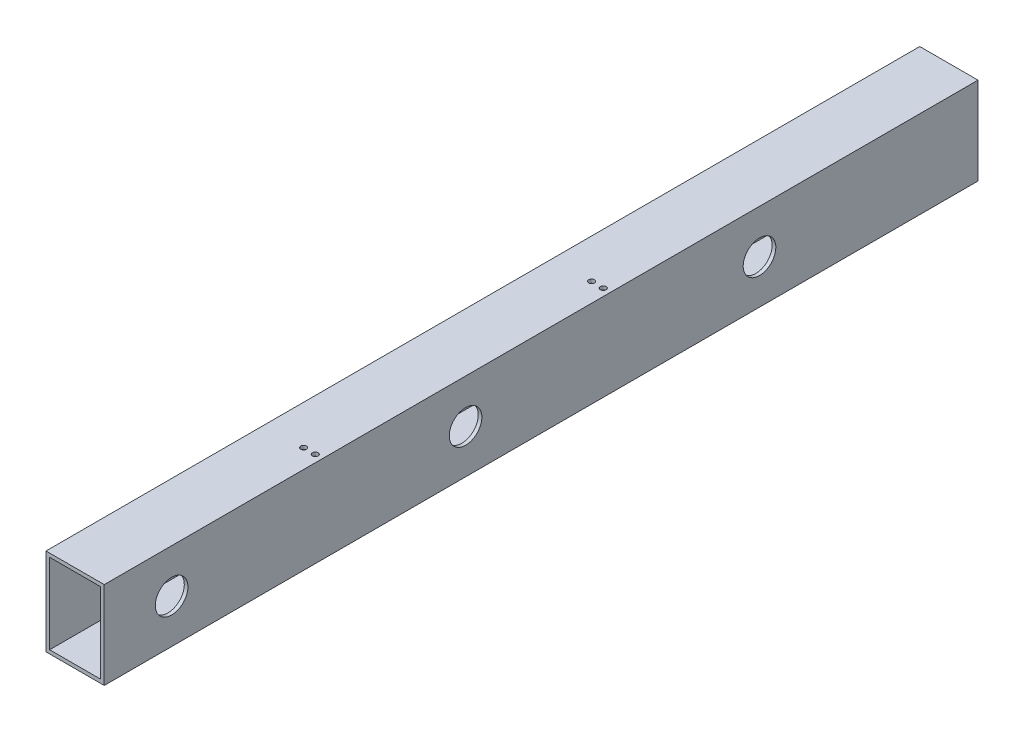
SolidWorks part; units mm, degrees
ref_plane "Front Plane" through (0, 0, 0) normal (0, 0, 1) x (1, 0, 0)
ref_plane "Top Plane" through (0, 0, 0) normal (0, 1, 0) x (1, 0, 0)
ref_plane "Right Plane" through (0, 0, 0) normal (1, 0, 0) x (0, 0, -1)
sketch "Sketch1" plane through (0, 0, 0) normal (0, 0, 1) x (1, 0, 0)
  line L0 (0, 38.1) -> (0, 34.925) construction
  line L1 (-25.4, 38.1) -> (25.4, 38.1)
  line L2 (-25.4, 38.1) -> (-25.4, -38.1)
  line L3 (-25.4, -38.1) -> (25.4, -38.1)
  line L4 (25.4, 38.1) -> (25.4, -38.1)
  line L5 (-25.4, 38.1) -> (25.4, -38.1) construction
  line L6 (-25.4, -38.1) -> (25.4, 38.1) construction
  line L7 (-22.225, 34.925) -> (22.225, 34.925)
  line L8 (-22.225, 34.925) -> (-22.225, -34.925)
  line L9 (-22.225, -34.925) -> (22.225, -34.925)
  line L10 (22.225, 34.925) -> (22.225, -34.925)
  line L11 (22.225, 0) -> (25.4, 0) construction
  line L12 (-22.225, 0) -> (-25.4, 0) construction
  line L13 (0, -34.925) -> (0, -38.1) construction
  point P0 (0, 0)
  dimension "D1" = 76.2
  dimension "D2" = 50.8
  dimension "D3" = 3.175
extrude "Boss-Extrude1" add sketch "Sketch1" along normal blind 762
sketch "Sketch2" plane through (0, 38.1, 0) normal (0, 1, 0) x (1, 0, 0)
  line L0 (-26.9875, -190.549) -> (26.9875, -190.549) construction
  line L1 (-25.4, 0) -> (25.4, 0)
  line L2 (-25.4, 0) -> (-25.4, -762)
  line L3 (-25.4, -762) -> (25.4, -762)
  line L4 (25.4, 0) -> (25.4, -762)
  line L5 (-26.4963, -703.2466) -> (26.4963, -703.2466) construction
  line L6 (0, -703.2466) -> (0, -190.549) construction
  line L7 (0, 0) -> (0, -190.549) construction
  line L8 (-74.6125, -402.6047) -> (-73.6301, -528.6965) construction
  line L9 (-74.1213, -465.6506) -> (-23.8125, -465.6506) construction
  line L10 (-23.8125, -465.6506) -> (26.9875, -465.6506) construction
  line L11 (21.8023, -571.6147) -> (25.4, -571.6147) construction
  line L12 (21.8023, -569.9256) -> (21.8023, -573.3038) construction
  line L13 (21.8023, -571.6147) -> (0, -571.6147) construction
  line L14 (0, -322.121) -> (25.4, -322.121) construction
  dimension "D1" = 190.549
  dimension "D2" = 512.6976
  dimension "D3" = 126.0917
  dimension "D4" = 50.3088
  dimension "D5" = 50.8
  dimension "D6" = 53.975
  dimension "D7" = 52.9926
  dimension "D8" = 275.1016
  dimension "D9" = 131.6319
  dimension "D10" = 131.572
ref_plane "Plane1" through (25.4, 0, 0) normal (1, 0, 0) x (0, 0, -1)
sketch "Sketch4" plane through (25.4, 0, 0) normal (1, 0, 0) x (0, 0, -1)
  line L0 (-703.2466, 38.1) -> (-703.2466, 0) construction
  line L1 (-703.2466, 38.1) -> (-190.549, 38.1) construction
  line L2 (-190.549, 38.1) -> (-190.549, 0) construction
  line L3 (0, 38.1) -> (-190.549, 38.1) construction
  line L4 (-190.549, 0) -> (0, 0) construction
  line L5 (0, -38.1) -> (0, 38.1) construction
  line L6 (-190.549, 0) -> (-703.2466, 0) construction
  line L7 (-446.8978, 0) -> (-446.8978, 38.1) construction
  line L8 (-402.6047, 38.1) -> (-528.6965, 38.1) construction
  circle A0 centre (-703.2466, 0) radius 14.224
  circle A1 centre (-190.549, 0) radius 14.224
  circle A2 centre (-446.8978, 0) radius 14.224
  dimension "D1" = 28.448
  dimension "D2" = 512.6976
  dimension "D3" = 190.549
extrude "Cut-Extrude1" cut sketch "Sketch4" against normal up to surface (50.8 mm away) up to face at (-25.4, 0, 381)
ref_plane "Plane2" through (0, 38.1, 0) normal (0, 1, 0) x (1, 0, 0)
sketch "Sketch5" plane through (0, 38.1, 0) normal (0, 1, 0) x (1, 0, 0)
  line L0 (5.08, -571.6147) -> (25.4, -571.6147) construction
  line L1 (21.8023, -571.6147) -> (0, -571.6147) construction
  line L2 (25.4, -575.4247) -> (5.08, -575.4247) construction
  line L3 (15.24, -320.4738) -> (15.24, -569.9675) construction
  line L4 (0, -322.121) -> (25.4, -322.121) construction
  line L5 (22.86, -324.2838) -> (22.86, -316.6638) construction
  line L6 (25.4, -571.6147) -> (25.4, -567.8047) construction
  line L7 (25.4, 0) -> (25.4, -762) construction
  line L8 (25.4, -567.8047) -> (5.08, -567.8047) construction
  line L9 (5.08, -567.8047) -> (5.08, -575.4247) construction
  line L10 (22.86, -567.8047) -> (22.86, -575.4247) construction
  line L11 (15.24, -571.6147) -> (15.24, -322.121) construction
  line L12 (15.24, -446.0443) -> (0, -446.0443) construction
  line L13 (0, -703.2466) -> (0, -190.549) construction
  line L14 (15.24, -446.0443) -> (25.4, -446.0443) construction
  line L15 (5.08, -324.2838) -> (5.08, -316.6638) construction
  line L16 (25.4, -324.2838) -> (5.08, -324.2838) construction
  line L17 (25.4, -316.6638) -> (5.08, -316.6638) construction
  line L18 (5.08, -320.4738) -> (25.4, -320.4738) construction
  circle A4 centre (8.89, -571.6147) radius 2.5006
  circle A5 centre (19.05, -571.6147) radius 2.5006
  circle A6 centre (19.05, -320.4738) radius 2.5006
  circle A7 centre (8.89, -320.4738) radius 2.5006
  dimension "D1" = 5.0013
  dimension "D2" = 2.54
  dimension "D5" = 3.81
  dimension "D6" = 3.81
  dimension "D7" = 20.32
  dimension "D8" = 3.81
extrude "Cut-Extrude2" cut sketch "Sketch5" against normal up to surface (3.175 mm away) up to face at (0, 34.925, 381)
